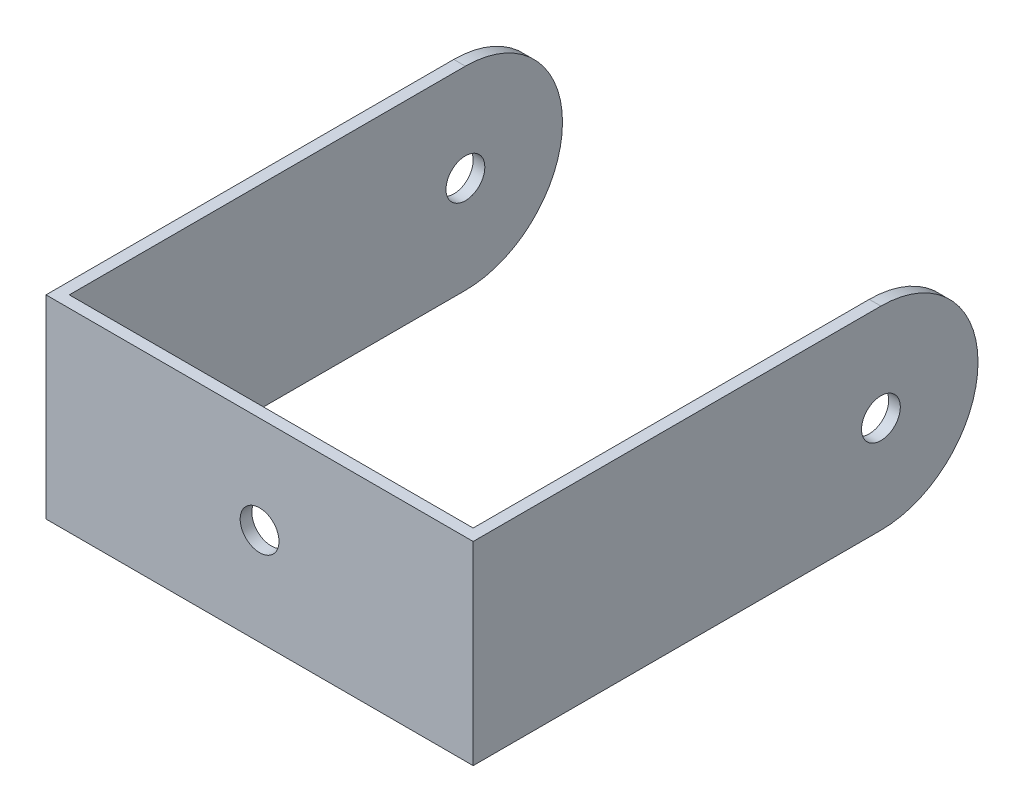
SolidWorks part; units mm, degrees
ref_plane "Front Plane" through (0, 0, 0) normal (0, 0, 1) x (1, 0, 0)
ref_plane "Top Plane" through (0, 0, 0) normal (0, 1, 0) x (1, 0, 0)
ref_plane "Right Plane" through (0, 0, 0) normal (1, 0, 0) x (0, 0, -1)
sketch "Sketch1" plane through (0, 0, 0) normal (0, 1, 0) x (1, 0, 0)
  line L0 (26, -31) -> (26, 32.5)
  line L1 (27.5, -32.5) -> (-27.5, -32.5)
  line L2 (27.5, -32.5) -> (27.5, 32.5)
  line L3 (27.5, 32.5) -> (-27.5, 32.5) construction
  line L4 (-27.5, -32.5) -> (-27.5, 32.5)
  line L5 (27.5, -32.5) -> (-27.5, 32.5) construction
  line L6 (27.5, 32.5) -> (-27.5, -32.5) construction
  line L7 (26, -31) -> (-26, -31)
  line L8 (-26, -31) -> (-26, 32.5)
  line L9 (-27.5, 32.5) -> (-26, 32.5)
  line L10 (26, 32.5) -> (27.5, 32.5)
  point P0 (0, 0)
  dimension "D1" = 65
  dimension "D2" = 55
  dimension "D3" = 1.5
extrude "Boss-Extrude1" add sketch "Sketch1" along normal mid plane 25
fillet "Fillet1" radius 12.5 4 edges at (-26.75, -12.5, -32.5) (-26.75, 12.5, -32.5) (26.75, -12.5, -32.5) (26.75, 12.5, -32.5)
sketch "Sketch2" plane through (0, 0, 0) normal (1, 0, 0) x (0, 0, -1)
  circle A0 centre (20, 0) radius 2.5
extrude "Cut-Extrude1" cut sketch "Sketch2" against normal through all both and the other way through all
mirror "Mirror1" [suppressed]
sketch "Sketch3" plane through (0, 0, 32.5) normal (0, 0, 1) x (1, 0, 0)
  circle A0 centre (0, 0) radius 2.5
extrude "Cut-Extrude2" cut sketch "Sketch3" against normal blind 10
